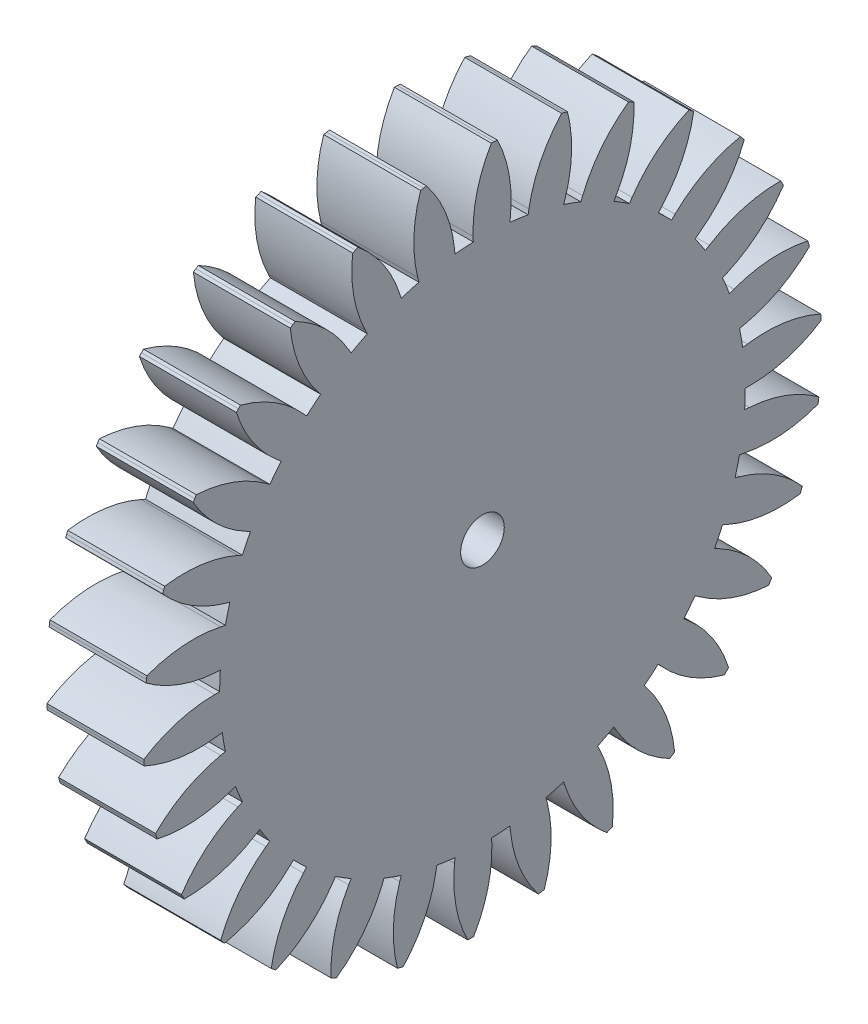
SolidWorks part; units mm, degrees
ref_plane "Front Plane" through (0, 0, 0) normal (0, 0, 1) x (1, 0, 0)
ref_plane "Top Plane" through (0, 0, 0) normal (0, 1, 0) x (1, 0, 0)
ref_plane "Right Plane" through (0, 0, 0) normal (1, 0, 0) x (0, 0, -1)
sketch "Sketch1" plane through (0, 0, 0) normal (1, 0, 0) x (0, 0, -1)
  line L0 (0, 0) -> (35, 0) construction
  line L1 (0, 0) -> (34.9347, 2.1367) construction
  line L2 (0, 0) -> (34.9147, 2.4415) construction
  line L3 (0, 0) -> (34.8921, 2.7461) construction
  line L4 (0, 0) -> (34.4683, 6.0777) construction
  line L5 (27.1081, 0) -> (27.6081, 0)
  line L6 (34.9347, 2.1367) -> (34.9147, 2.4415)
  line L7 (34.8921, 2.7461) -> (34.9147, 2.4415)
  line L8 (26.8442, 3.7727) -> (27.3394, 3.8423)
  line L9 (26.5157, -5.6361) -> (27.0048, -5.74)
  line L10 (34.6156, -5.1733) -> (34.6594, -4.8711)
  line L11 (34.7006, -4.5684) -> (34.6594, -4.8711)
  line L12 (27.042, -1.891) -> (27.5408, -1.9258)
  line L13 (0, 0) -> (34.6594, -4.8711) construction
  line L14 (24.7644, -11.0258) -> (25.2212, -11.2292)
  line L15 (32.7835, -12.2573) -> (32.8892, -11.9707)
  line L16 (32.9925, -11.6832) -> (32.8892, -11.9707)
  line L17 (26.0579, -7.472) -> (26.5386, -7.6098)
  line L18 (0, 0) -> (32.8892, -11.9707) construction
  line L19 (21.9309, -15.9337) -> (22.3354, -16.2276)
  line L20 (29.5187, -18.8055) -> (29.6817, -18.5472)
  line L21 (29.8424, -18.2874) -> (29.6817, -18.5472)
  line L22 (23.935, -12.7265) -> (24.3765, -12.9612)
  line L23 (0, 0) -> (29.6817, -18.5472) construction
  line L24 (18.1388, -20.1452) -> (18.4734, -20.5168)
  line L25 (24.9638, -24.5318) -> (25.1769, -24.313)
  line L26 (25.3881, -24.0924) -> (25.1769, -24.313)
  line L27 (20.766, -17.4247) -> (21.149, -17.7461)
  line L28 (0, 0) -> (25.1769, -24.313) construction
  line L29 (13.554, -23.4763) -> (13.804, -23.9093)
  line L30 (19.3178, -29.186) -> (19.5718, -29.0163)
  line L31 (19.8242, -28.8444) -> (19.5718, -29.0163)
  line L32 (16.6894, -21.3614) -> (16.9972, -21.7555)
  line L33 (0, 0) -> (19.5718, -29.0163) construction
  line L34 (8.3769, -25.7813) -> (8.5314, -26.2568)
  line L35 (12.8275, -32.5646) -> (13.1112, -32.4514)
  line L36 (13.3939, -32.3358) -> (13.1112, -32.4514)
  line L37 (11.8834, -24.3646) -> (12.1026, -24.814)
  line L38 (0, 0) -> (13.1112, -32.4514) construction
  line L39 (2.8336, -26.9596) -> (2.8858, -27.4568)
  line L40 (5.7767, -34.52) -> (6.0777, -34.4683)
  line L41 (6.3782, -34.4139) -> (6.0777, -34.4683)
  line L42 (6.558, -26.3028) -> (6.679, -26.788)
  line L43 (0, 0) -> (6.0777, -34.4683) construction
  line L44 (-2.8336, -26.9596) -> (-2.8858, -27.4568)
  line L45 (-1.5267, -34.9667) -> (-1.2215, -34.9787)
  line L46 (-0.9162, -34.988) -> (-1.2215, -34.9787)
  line L47 (0.9461, -27.0915) -> (0.9635, -27.5912)
  line L48 (0, 0) -> (-1.2215, -34.9787) construction
  line L49 (-8.3769, -25.7813) -> (-8.5314, -26.2568)
  line L50 (-8.7633, -33.8852) -> (-8.4673, -33.9604)
  line L51 (-8.1706, -34.0329) -> (-8.4673, -33.9604)
  line L52 (-4.7073, -26.6962) -> (-4.7941, -27.1886)
  line L53 (0, 0) -> (-8.4673, -33.9604) construction
  line L54 (-13.554, -23.4763) -> (-13.804, -23.9093)
  line L55 (-15.6169, -31.3227) -> (-15.343, -31.4578)
  line L56 (-15.0679, -31.5905) -> (-15.343, -31.4578)
  line L57 (-10.1549, -25.1342) -> (-10.3422, -25.5978)
  line L58 (0, 0) -> (-15.343, -31.4578) construction
  line L59 (-18.1388, -20.1452) -> (-18.4734, -20.5168)
  line L60 (-21.788, -27.3913) -> (-21.5482, -27.5804)
  line L61 (-21.3067, -27.7674) -> (-21.5482, -27.5804)
  line L62 (-15.1586, -22.4736) -> (-15.4382, -22.8881)
  line L63 (0, 0) -> (-21.5482, -27.5804) construction
  line L64 (-21.9309, -15.9337) -> (-22.3354, -16.2276)
  line L65 (-27.0069, -22.2627) -> (-26.8116, -22.4976)
  line L66 (-26.6142, -22.7307) -> (-26.8116, -22.4976)
  line L67 (-19.4999, -18.8308) -> (-19.8596, -19.1782)
  line L68 (0, 0) -> (-26.8116, -22.4976) construction
  line L69 (-24.7644, -11.0258) -> (-25.2212, -11.2292)
  line L70 (-31.0454, -16.1612) -> (-30.9032, -16.4315)
  line L71 (-30.7586, -16.7006) -> (-30.9032, -16.4315)
  line L72 (-22.9889, -14.3651) -> (-23.413, -14.63)
  line L73 (0, 0) -> (-30.9032, -16.4315) construction
  line L74 (-26.5157, -5.6361) -> (-27.0048, -5.74)
  line L75 (-33.7271, -9.3533) -> (-33.6442, -9.6473)
  line L76 (-33.5587, -9.9405) -> (-33.6442, -9.6473)
  line L77 (-25.4732, -9.2715) -> (-25.9431, -9.4425)
  line L78 (0, 0) -> (-33.6442, -9.6473) construction
  line L79 (-27.1081, 0) -> (-27.6081, 0)
  line L80 (-34.9347, -2.1367) -> (-34.9147, -2.4415)
  line L81 (-34.8921, -2.7461) -> (-34.9147, -2.4415)
  line L82 (-26.8442, -3.7727) -> (-27.3394, -3.8423)
  line L83 (0, 0) -> (-34.9147, -2.4415) construction
  line L84 (-26.5157, 5.6361) -> (-27.0048, 5.74)
  line L85 (-34.6156, 5.1733) -> (-34.6594, 4.8711)
  line L86 (-34.7006, 4.5684) -> (-34.6594, 4.8711)
  line L87 (-27.042, 1.891) -> (-27.5408, 1.9258)
  line L88 (0, 0) -> (-34.6594, 4.8711) construction
  line L89 (-24.7644, 11.0258) -> (-25.2212, 11.2292)
  line L90 (-32.7835, 12.2573) -> (-32.8892, 11.9707)
  line L91 (-32.9925, 11.6832) -> (-32.8892, 11.9707)
  line L92 (-26.0579, 7.472) -> (-26.5386, 7.6098)
  line L93 (0, 0) -> (-32.8892, 11.9707) construction
  line L94 (-21.9309, 15.9337) -> (-22.3354, 16.2276)
  line L95 (-29.5187, 18.8055) -> (-29.6817, 18.5472)
  line L96 (-29.8424, 18.2874) -> (-29.6817, 18.5472)
  line L97 (-23.935, 12.7265) -> (-24.3765, 12.9612)
  line L98 (0, 0) -> (-29.6817, 18.5472) construction
  line L99 (-18.1388, 20.1452) -> (-18.4734, 20.5168)
  line L100 (-24.9638, 24.5318) -> (-25.1769, 24.313)
  line L101 (-25.3881, 24.0924) -> (-25.1769, 24.313)
  line L102 (-20.766, 17.4247) -> (-21.149, 17.7461)
  line L103 (0, 0) -> (-25.1769, 24.313) construction
  line L104 (-13.554, 23.4763) -> (-13.804, 23.9093)
  line L105 (-19.3178, 29.186) -> (-19.5718, 29.0163)
  line L106 (-19.8242, 28.8444) -> (-19.5718, 29.0163)
  line L107 (-16.6894, 21.3614) -> (-16.9972, 21.7555)
  line L108 (0, 0) -> (-19.5718, 29.0163) construction
  line L109 (-8.3769, 25.7813) -> (-8.5314, 26.2568)
  line L110 (-12.8275, 32.5646) -> (-13.1112, 32.4514)
  line L111 (-13.3939, 32.3358) -> (-13.1112, 32.4514)
  line L112 (-11.8834, 24.3646) -> (-12.1026, 24.814)
  line L113 (0, 0) -> (-13.1112, 32.4514) construction
  line L114 (-2.8336, 26.9596) -> (-2.8858, 27.4568)
  line L115 (-5.7767, 34.52) -> (-6.0777, 34.4683)
  line L116 (-6.3782, 34.4139) -> (-6.0777, 34.4683)
  line L117 (-6.558, 26.3028) -> (-6.679, 26.788)
  line L118 (0, 0) -> (-6.0777, 34.4683) construction
  line L119 (2.8336, 26.9596) -> (2.8858, 27.4568)
  line L120 (1.5267, 34.9667) -> (1.2215, 34.9787)
  line L121 (0.9162, 34.988) -> (1.2215, 34.9787)
  line L122 (-0.9461, 27.0915) -> (-0.9635, 27.5912)
  line L123 (0, 0) -> (1.2215, 34.9787) construction
  line L124 (8.3769, 25.7813) -> (8.5314, 26.2568)
  line L125 (8.7633, 33.8852) -> (8.4673, 33.9604)
  line L126 (8.1706, 34.0329) -> (8.4673, 33.9604)
  line L127 (4.7073, 26.6962) -> (4.7941, 27.1886)
  line L128 (0, 0) -> (8.4673, 33.9604) construction
  line L129 (13.554, 23.4763) -> (13.804, 23.9093)
  line L130 (15.6169, 31.3227) -> (15.343, 31.4578)
  line L131 (15.0679, 31.5905) -> (15.343, 31.4578)
  line L132 (10.1549, 25.1342) -> (10.3422, 25.5978)
  line L133 (0, 0) -> (15.343, 31.4578) construction
  line L134 (18.1388, 20.1452) -> (18.4734, 20.5168)
  line L135 (21.788, 27.3913) -> (21.5482, 27.5804)
  line L136 (21.3067, 27.7674) -> (21.5482, 27.5804)
  line L137 (15.1586, 22.4736) -> (15.4382, 22.8881)
  line L138 (0, 0) -> (21.5482, 27.5804) construction
  line L139 (21.9309, 15.9337) -> (22.3354, 16.2276)
  line L140 (27.0069, 22.2627) -> (26.8116, 22.4976)
  line L141 (26.6142, 22.7307) -> (26.8116, 22.4976)
  line L142 (19.4999, 18.8308) -> (19.8596, 19.1782)
  line L143 (0, 0) -> (26.8116, 22.4976) construction
  line L144 (24.7644, 11.0258) -> (25.2212, 11.2292)
  line L145 (31.0454, 16.1612) -> (30.9032, 16.4315)
  line L146 (30.7586, 16.7006) -> (30.9032, 16.4315)
  line L147 (22.9889, 14.3651) -> (23.413, 14.63)
  line L148 (0, 0) -> (30.9032, 16.4315) construction
  line L149 (26.5157, 5.6361) -> (27.0048, 5.74)
  line L150 (33.7271, 9.3533) -> (33.6442, 9.6473)
  line L151 (33.5587, 9.9405) -> (33.6442, 9.6473)
  line L152 (25.4732, 9.2715) -> (25.9431, 9.4425)
  line L153 (0, 0) -> (33.6442, 9.6473) construction
  circle A0 centre (0, 0) radius 2.25
  circle A1 centre (0, 0) radius 27.1081
  circle A2 centre (0, 0) radius 35 construction
  arc A3 (27.6081, 0) -> (34.9347, 2.1367) centre (27.6081, 13.6298) ccw
  arc A4 (27.3394, 3.8423) -> (34.8921, 2.7461) centre (29.2363, -9.6548) cw
  arc A5 (27.0048, -5.74) -> (34.6156, -5.1733) centre (29.8385, 7.5919) ccw
  arc A6 (27.5408, -1.9258) -> (34.7006, -4.5684) centre (26.59, -15.5224) cw
  arc A7 (25.2212, -11.2292) -> (32.7835, -12.2573) centre (30.7649, 1.2222) ccw
  arc A8 (26.5386, -7.6098) -> (32.9925, -11.6832) centre (22.7817, -20.7116) cw
  arc A9 (22.3354, -16.2276) -> (29.5187, -18.8055) centre (30.3468, -5.2009) ccw
  arc A10 (24.3765, -12.9612) -> (29.8424, -18.2874) centre (17.9777, -24.9956) cw
  arc A11 (18.4734, -20.5168) -> (24.9638, -24.5318) centre (28.6023, -11.3967) ccw
  arc A12 (21.149, -17.7461) -> (25.3881, -24.0924) centre (12.388, -28.1871) cw
  arc A13 (13.804, -23.9093) -> (19.3178, -29.186) centre (25.6077, -17.0944) ccw
  arc A14 (16.9972, -21.7555) -> (19.8242, -28.8444) centre (6.2568, -30.1468) cw
  arc A15 (8.5314, -26.2568) -> (12.8275, -32.5646) centre (21.494, -22.045) ccw
  arc A16 (12.1026, -24.814) -> (13.3939, -32.3358) centre (-0.1478, -30.7889) cw
  arc A17 (2.8858, -27.4568) -> (5.7767, -34.52) centre (16.4409, -26.0321) ccw
  arc A18 (6.679, -26.788) -> (6.3782, -34.4139) centre (-6.5459, -30.0853) cw
  arc A19 (-2.8858, -27.4568) -> (-1.5267, -34.9667) centre (10.6693, -28.8815) ccw
  arc A20 (0.9635, -27.5912) -> (-0.9162, -34.988) centre (-12.6579, -28.0669) cw
  arc A21 (-8.5314, -26.2568) -> (-8.7633, -33.8852) centre (4.4313, -30.4687) ccw
  arc A22 (-4.7941, -27.1886) -> (-8.1706, -34.0329) centre (-18.2168, -24.8219) cw
  arc A23 (-13.804, -23.9093) -> (-15.6169, -31.3227) centre (-2.0003, -30.7242) ccw
  arc A24 (-10.3422, -25.5978) -> (-15.0679, -31.5905) centre (-22.9794, -20.492) cw
  arc A25 (-18.4734, -20.5168) -> (-21.788, -27.3913) centre (-8.3445, -29.6369) ccw
  arc A26 (-15.4382, -22.8881) -> (-21.3067, -27.7674) centre (-26.7378, -15.2665) cw
  arc A27 (-22.3354, -16.2276) -> (-27.0069, -22.2627) centre (-14.324, -27.2543) ccw
  arc A28 (-19.8596, -19.1782) -> (-26.6142, -22.7307) centre (-29.3276, -9.3737) cw
  arc A29 (-25.2212, -11.2292) -> (-31.0454, -16.1612) centre (-19.6775, -23.6806) ccw
  arc A30 (-23.413, -14.63) -> (-30.7586, -16.7006) centre (-30.6356, -3.0714) cw
  arc A31 (-27.0048, -5.74) -> (-33.7271, -9.3533) centre (-24.171, -19.0719) ccw
  arc A32 (-25.9431, -9.4425) -> (-33.5587, -9.9405) centre (-30.6047, 3.3653) cw
  arc A33 (-27.6081, 0) -> (-34.9347, -2.1367) centre (-27.6081, -13.6298) ccw
  arc A34 (-27.3394, -3.8423) -> (-34.8921, -2.7461) centre (-29.2363, 9.6548) cw
  arc A35 (-27.0048, 5.74) -> (-34.6156, 5.1733) centre (-29.8385, -7.5919) ccw
  arc A36 (-27.5408, 1.9258) -> (-34.7006, 4.5684) centre (-26.59, 15.5224) cw
  arc A37 (-25.2212, 11.2292) -> (-32.7835, 12.2573) centre (-30.7649, -1.2222) ccw
  arc A38 (-26.5386, 7.6098) -> (-32.9925, 11.6832) centre (-22.7817, 20.7116) cw
  arc A39 (-22.3354, 16.2276) -> (-29.5187, 18.8055) centre (-30.3468, 5.2009) ccw
  arc A40 (-24.3765, 12.9612) -> (-29.8424, 18.2874) centre (-17.9777, 24.9956) cw
  arc A41 (-18.4734, 20.5168) -> (-24.9638, 24.5318) centre (-28.6023, 11.3967) ccw
  arc A42 (-21.149, 17.7461) -> (-25.3881, 24.0924) centre (-12.388, 28.1871) cw
  arc A43 (-13.804, 23.9093) -> (-19.3178, 29.186) centre (-25.6077, 17.0944) ccw
  arc A44 (-16.9972, 21.7555) -> (-19.8242, 28.8444) centre (-6.2568, 30.1468) cw
  arc A45 (-8.5314, 26.2568) -> (-12.8275, 32.5646) centre (-21.494, 22.045) ccw
  arc A46 (-12.1026, 24.814) -> (-13.3939, 32.3358) centre (0.1478, 30.7889) cw
  arc A47 (-2.8858, 27.4568) -> (-5.7767, 34.52) centre (-16.4409, 26.0321) ccw
  arc A48 (-6.679, 26.788) -> (-6.3782, 34.4139) centre (6.5459, 30.0853) cw
  arc A49 (2.8858, 27.4568) -> (1.5267, 34.9667) centre (-10.6693, 28.8815) ccw
  arc A50 (-0.9635, 27.5912) -> (0.9162, 34.988) centre (12.6579, 28.0669) cw
  arc A51 (8.5314, 26.2568) -> (8.7633, 33.8852) centre (-4.4313, 30.4687) ccw
  arc A52 (4.7941, 27.1886) -> (8.1706, 34.0329) centre (18.2168, 24.8219) cw
  arc A53 (13.804, 23.9093) -> (15.6169, 31.3227) centre (2.0003, 30.7242) ccw
  arc A54 (10.3422, 25.5978) -> (15.0679, 31.5905) centre (22.9794, 20.492) cw
  arc A55 (18.4734, 20.5168) -> (21.788, 27.3913) centre (8.3445, 29.6369) ccw
  arc A56 (15.4382, 22.8881) -> (21.3067, 27.7674) centre (26.7378, 15.2665) cw
  arc A57 (22.3354, 16.2276) -> (27.0069, 22.2627) centre (14.324, 27.2543) ccw
  arc A58 (19.8596, 19.1782) -> (26.6142, 22.7307) centre (29.3276, 9.3737) cw
  arc A59 (25.2212, 11.2292) -> (31.0454, 16.1612) centre (19.6775, 23.6806) ccw
  arc A60 (23.413, 14.63) -> (30.7586, 16.7006) centre (30.6356, 3.0714) cw
  arc A61 (27.0048, 5.74) -> (33.7271, 9.3533) centre (24.171, 19.0719) ccw
  arc A62 (25.9431, 9.4425) -> (33.5587, 9.9405) centre (30.6047, -3.3653) cw
  point P10 (34.4683, 6.0777)
  point P11 (34.8921, 2.7461)
  point P12 (34.9147, 2.4415)
  point P13 (34.9347, 2.1367)
  point P14 (27.1081, 0)
  point P19 (34.9247, 2.2891)
  point P20 (34.9034, 2.5938)
  point P182 (0, 0)
  point P379 (0, 0)
  dimension "D1" = 4.5
  dimension "D3" = 70
  dimension "D4" = 4
  dimension "D5" = 4.5
  dimension "D6" = 3.5
  dimension "D7" = 35
  dimension "D9" = 0.5
  dimension "D2" = 30
extrude "Boss-Extrude1" add sketch "Sketch1" along normal blind 10 contours A1 | A14 L32 A1 L29 A13 L30 L31 | A12 L27 A1 L24 A11 L25 L26 | A54 L132 A1 L129 A53 L130 L131 | A56 L137 A1 L134 A55 L135 L136 | A58 L142 A1 L139 A57 L140 L141 | A60 L147 A1 L144 A59 L145 L146 | A62 L152 A1 L149 A61 L150 L151 | A4 L8 A1 L5 A3 L6 L7 | A6 L12 A1 L9 A5 L10 L11 | A8 L17 A1 L14 A7 L15 L16 | A10 L22 A1 L19 A9 L20 L21 | A16 L37 A1 L34 A15 L35 L36 | A18 L42 A1 L39 A17 L40 L41 | A20 L47 A1 L44 A19 L45 L46 | A22 L52 A1 L49 A21 L50 L51 | A24 L57 A1 L54 A23 L55 L56 | A26 L62 A1 L59 A25 L60 L61 | A28 L67 A1 L64 A27 L65 L66 | A30 L72 A1 L69 A29 L70 L71 | A32 L77 A1 L74 A31 L75 L76 | A34 L82 A1 L79 A33 L80 L81 | A36 L87 A1 L84 A35 L85 L86 | A38 L92 A1 L89 A37 L90 L91 | A40 L97 A1 L94 A39 L95 L96 | A42 L102 A1 L99 A41 L100 L101 | A44 L107 A1 L104 A43 L105 L106 | A46 L112 A1 L109 A45 L110 L111 | A48 L117 A1 L114 A47 L115 L116 | A50 L122 A1 L119 A49 L120 L121 | A52 L127 A1 L124 A51 L125 L126 region at (0, 2.1182, -30.2924) region at (0, -0.9193, -26.3253) region at (0, -4.2262, -30.0708) region at (0, 8.3701, -29.19) region at (0, -10.3859, -28.535) region at (0, 14.2561, -26.8119) region at (0, -16.0917, -25.7521) region at (0, 19.5191, -23.262) region at (0, -21.0942, -21.8437) region at (0, 23.929, -18.6954) region at (0, -25.1748, -16.9806) region at (0, 27.2931, -13.3117) region at (0, -28.1552, -11.3754) region at (0, 29.4643, -7.3463) region at (0, -29.905, -5.2731) region at (0, 30.3478, -1.0598) region at (0, -30.3478, 1.0598) region at (0, 29.905, 5.2731) region at (0, -29.4643, 7.3463) region at (0, 28.1552, 11.3754) region at (0, -27.2931, 13.3117) region at (0, 25.1748, 16.9806) region at (0, -23.929, 18.6954) region at (0, 21.0942, 21.8437) region at (0, -19.5191, 23.262) region at (0, 16.0917, 25.7521) region at (0, -14.2561, 26.8119) region at (0, 10.3859, 28.535) region at (0, -8.3701, 29.19) region at (0, 4.2262, 30.0708) region at (0, -2.1182, 30.2924)
equation "\"Gear_angle\"= 8"
equation "\"D4@Sketch1\"=\"Gear_angle\"*0.5"
equation "\"D5@Sketch1\"=\"Gear_angle\"*0.5 +0.5"
equation "\"D6@Sketch1\"=\"Gear_angle\"*0.5 -0.5"
equation "\"Gear_diameter\"= 70mm"
equation "\"Gear_tooth_height\"= 2mm"
equation "\"gear_thickeness\"=10"
equation "\"D7@Sketch1\"=\"Gear_diameter\"*0.5"
equation "\"gear_thickness\"=10"
equation "\"D1@Boss-Extrude1\"=\"gear_thickness\""
